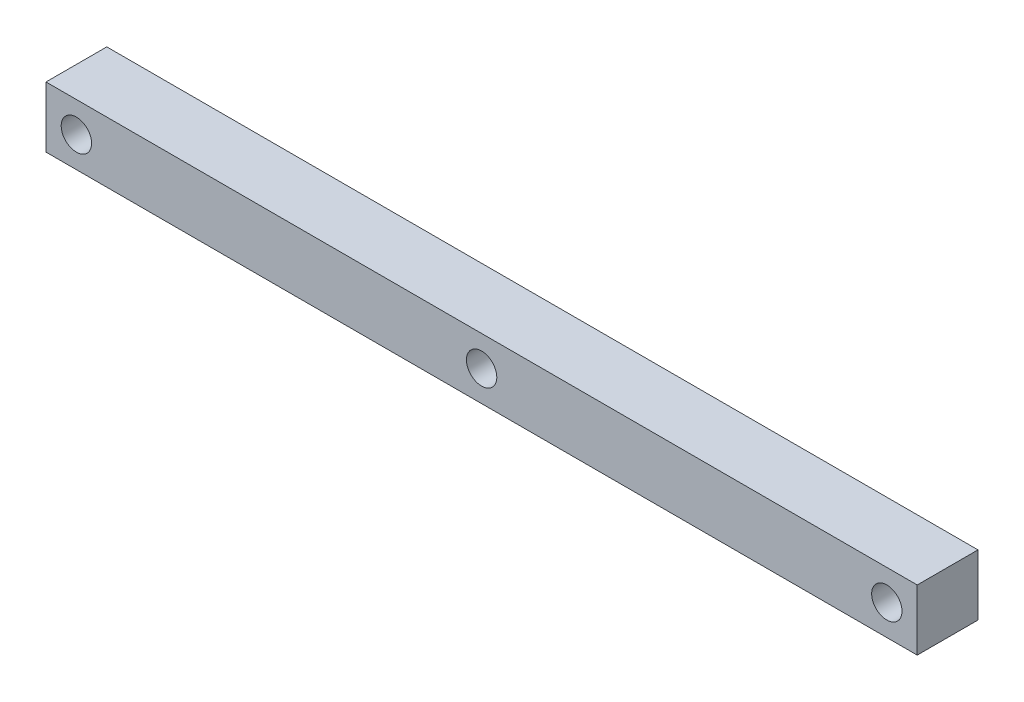
SolidWorks part; units mm, degrees
ref_plane "Front Plane" through (0, 0, 0) normal (0, 0, 1) x (1, 0, 0)
ref_plane "Top Plane" through (0, 0, 0) normal (0, 1, 0) x (1, 0, 0)
ref_plane "Right Plane" through (0, 0, 0) normal (1, 0, 0) x (0, 0, -1)
sketch "Sketch1" plane through (0, 0, 0) normal (0, 0, 1) x (1, 0, 0)
  line L0 (200, 0) -> (-200, 0) construction
  line L1 (215, 15) -> (-215, 15)
  line L2 (215, 15) -> (215, -15)
  line L3 (215, -15) -> (-215, -15)
  line L4 (-215, 15) -> (-215, -15)
  line L5 (215, 15) -> (-215, -15) construction
  line L6 (215, -15) -> (-215, 15) construction
  circle A0 centre (-200, 0) radius 7.5
  circle A1 centre (200, 0) radius 7.5
  circle A2 centre (0, 0) radius 7.5
  point P0 (0, 0)
  point P8 (0, 0)
  dimension "D2" = 15
  dimension "D1" = 30
  dimension "D3" = 400
  dimension "D4" = 15
extrude "Boss-Extrude1" add sketch "Sketch1" along normal mid plane 30
equation "\"A\"= 200"
equation "\"hole_diameter\"=15"
equation "\"D2@Sketch1\"=\"hole_diameter\""
equation "\"D3@Sketch1\"=2*\"A\""
equation "\"D4@Sketch1\"=\"hole_diameter\""
